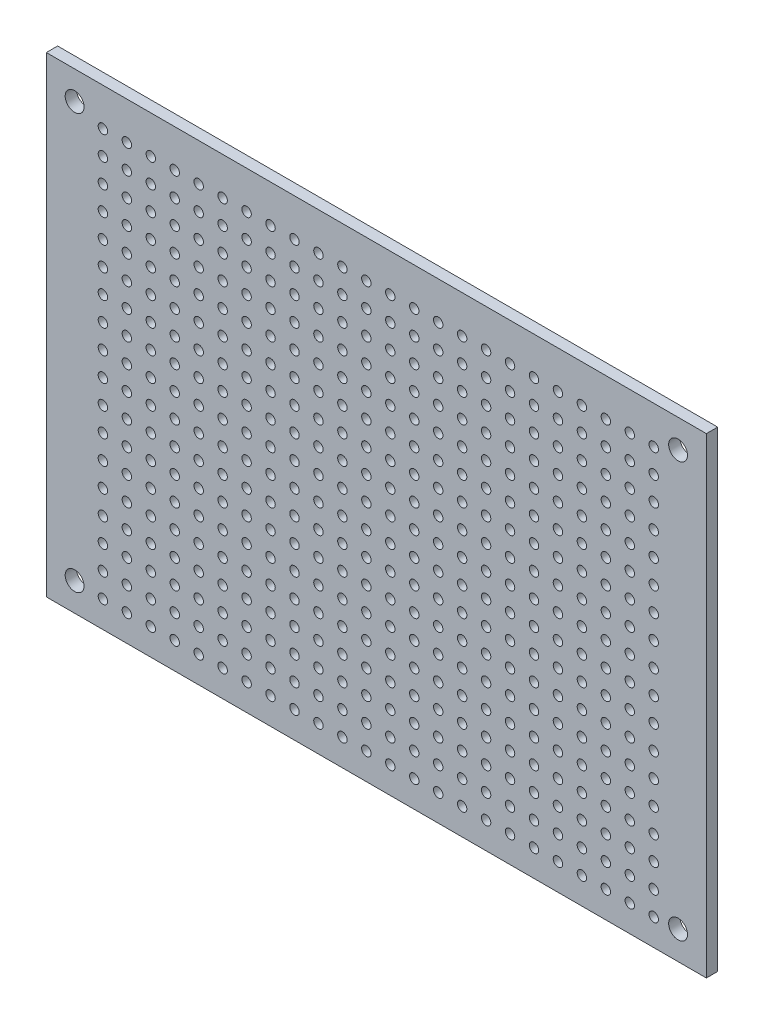
SolidWorks part; units mm, degrees
material "Ст 3 ГОСТ 380-88"
ref_plane "FRONT" through (0, 0, 0) normal (0, 0, 1) x (1, 0, 0)
ref_plane "TOP" through (0, 0, 0) normal (0, 1, 0) x (1, 0, 0)
ref_plane "RIGHT" through (0, 0, 0) normal (1, 0, 0) x (0, 0, -1)
sketch "Эскиз1" plane through (0, 0, 0) normal (0, 0, 1) x (1, 0, 0)
  line L0 (35, 50) -> (35, 0) construction
  line L1 (0, 0) -> (70, 0)
  line L2 (0, 0) -> (0, 50)
  line L3 (0, 50) -> (70, 50)
  line L4 (70, 0) -> (70, 50)
  line L5 (70, 25) -> (0, 25) construction
  line L6 (6, 46) -> (64.42, 46) construction
  line L7 (6, 46) -> (6, 2.82) construction
  circle A0 centre (6, 46) radius 0.5
  circle A1 centre (3, 47) radius 1
  circle A2 centre (67, 47) radius 1
  circle A3 centre (67, 3) radius 1
  circle A4 centre (3, 3) radius 1
  circle A5 centre (8.54, 46) radius 0.5
  circle A6 centre (11.08, 46) radius 0.5
  circle A7 centre (13.62, 46) radius 0.5
  circle A8 centre (16.16, 46) radius 0.5
  circle A9 centre (18.7, 46) radius 0.5
  circle A10 centre (21.24, 46) radius 0.5
  circle A11 centre (23.78, 46) radius 0.5
  circle A12 centre (26.32, 46) radius 0.5
  circle A13 centre (28.86, 46) radius 0.5
  circle A14 centre (31.4, 46) radius 0.5
  circle A15 centre (33.94, 46) radius 0.5
  circle A16 centre (36.48, 46) radius 0.5
  circle A17 centre (39.02, 46) radius 0.5
  circle A18 centre (41.56, 46) radius 0.5
  circle A19 centre (44.1, 46) radius 0.5
  circle A20 centre (46.64, 46) radius 0.5
  circle A21 centre (49.18, 46) radius 0.5
  circle A22 centre (51.72, 46) radius 0.5
  circle A23 centre (54.26, 46) radius 0.5
  circle A24 centre (56.8, 46) radius 0.5
  circle A25 centre (59.34, 46) radius 0.5
  circle A26 centre (61.88, 46) radius 0.5
  circle A27 centre (64.42, 46) radius 0.5
  circle A28 centre (8.54, 43.46) radius 0.5
  circle A29 centre (11.08, 43.46) radius 0.5
  circle A30 centre (13.62, 43.46) radius 0.5
  circle A31 centre (16.16, 43.46) radius 0.5
  circle A32 centre (18.7, 43.46) radius 0.5
  circle A33 centre (21.24, 43.46) radius 0.5
  circle A34 centre (23.78, 43.46) radius 0.5
  circle A35 centre (26.32, 43.46) radius 0.5
  circle A36 centre (28.86, 43.46) radius 0.5
  circle A37 centre (31.4, 43.46) radius 0.5
  circle A38 centre (33.94, 43.46) radius 0.5
  circle A39 centre (36.48, 43.46) radius 0.5
  circle A40 centre (39.02, 43.46) radius 0.5
  circle A41 centre (41.56, 43.46) radius 0.5
  circle A42 centre (44.1, 43.46) radius 0.5
  circle A43 centre (46.64, 43.46) radius 0.5
  circle A44 centre (49.18, 43.46) radius 0.5
  circle A45 centre (51.72, 43.46) radius 0.5
  circle A46 centre (54.26, 43.46) radius 0.5
  circle A47 centre (56.8, 43.46) radius 0.5
  circle A48 centre (59.34, 43.46) radius 0.5
  circle A49 centre (61.88, 43.46) radius 0.5
  circle A50 centre (64.42, 43.46) radius 0.5
  circle A51 centre (8.54, 40.92) radius 0.5
  circle A52 centre (11.08, 40.92) radius 0.5
  circle A53 centre (13.62, 40.92) radius 0.5
  circle A54 centre (16.16, 40.92) radius 0.5
  circle A55 centre (18.7, 40.92) radius 0.5
  circle A56 centre (21.24, 40.92) radius 0.5
  circle A57 centre (23.78, 40.92) radius 0.5
  circle A58 centre (26.32, 40.92) radius 0.5
  circle A59 centre (28.86, 40.92) radius 0.5
  circle A60 centre (31.4, 40.92) radius 0.5
  circle A61 centre (33.94, 40.92) radius 0.5
  circle A62 centre (36.48, 40.92) radius 0.5
  circle A63 centre (39.02, 40.92) radius 0.5
  circle A64 centre (41.56, 40.92) radius 0.5
  circle A65 centre (44.1, 40.92) radius 0.5
  circle A66 centre (46.64, 40.92) radius 0.5
  circle A67 centre (49.18, 40.92) radius 0.5
  circle A68 centre (51.72, 40.92) radius 0.5
  circle A69 centre (54.26, 40.92) radius 0.5
  circle A70 centre (56.8, 40.92) radius 0.5
  circle A71 centre (59.34, 40.92) radius 0.5
  circle A72 centre (61.88, 40.92) radius 0.5
  circle A73 centre (64.42, 40.92) radius 0.5
  circle A74 centre (8.54, 38.38) radius 0.5
  circle A75 centre (11.08, 38.38) radius 0.5
  circle A76 centre (13.62, 38.38) radius 0.5
  circle A77 centre (16.16, 38.38) radius 0.5
  circle A78 centre (18.7, 38.38) radius 0.5
  circle A79 centre (21.24, 38.38) radius 0.5
  circle A80 centre (23.78, 38.38) radius 0.5
  circle A81 centre (26.32, 38.38) radius 0.5
  circle A82 centre (28.86, 38.38) radius 0.5
  circle A83 centre (31.4, 38.38) radius 0.5
  circle A84 centre (33.94, 38.38) radius 0.5
  circle A85 centre (36.48, 38.38) radius 0.5
  circle A86 centre (39.02, 38.38) radius 0.5
  circle A87 centre (41.56, 38.38) radius 0.5
  circle A88 centre (44.1, 38.38) radius 0.5
  circle A89 centre (46.64, 38.38) radius 0.5
  circle A90 centre (49.18, 38.38) radius 0.5
  circle A91 centre (51.72, 38.38) radius 0.5
  circle A92 centre (54.26, 38.38) radius 0.5
  circle A93 centre (56.8, 38.38) radius 0.5
  circle A94 centre (59.34, 38.38) radius 0.5
  circle A95 centre (61.88, 38.38) radius 0.5
  circle A96 centre (64.42, 38.38) radius 0.5
  circle A97 centre (8.54, 35.84) radius 0.5
  circle A98 centre (11.08, 35.84) radius 0.5
  circle A99 centre (13.62, 35.84) radius 0.5
  circle A100 centre (16.16, 35.84) radius 0.5
  circle A101 centre (18.7, 35.84) radius 0.5
  circle A102 centre (21.24, 35.84) radius 0.5
  circle A103 centre (23.78, 35.84) radius 0.5
  circle A104 centre (26.32, 35.84) radius 0.5
  circle A105 centre (28.86, 35.84) radius 0.5
  circle A106 centre (31.4, 35.84) radius 0.5
  circle A107 centre (33.94, 35.84) radius 0.5
  circle A108 centre (36.48, 35.84) radius 0.5
  circle A109 centre (39.02, 35.84) radius 0.5
  circle A110 centre (41.56, 35.84) radius 0.5
  circle A111 centre (44.1, 35.84) radius 0.5
  circle A112 centre (46.64, 35.84) radius 0.5
  circle A113 centre (49.18, 35.84) radius 0.5
  circle A114 centre (51.72, 35.84) radius 0.5
  circle A115 centre (54.26, 35.84) radius 0.5
  circle A116 centre (56.8, 35.84) radius 0.5
  circle A117 centre (59.34, 35.84) radius 0.5
  circle A118 centre (61.88, 35.84) radius 0.5
  circle A119 centre (64.42, 35.84) radius 0.5
  circle A120 centre (8.54, 33.3) radius 0.5
  circle A121 centre (11.08, 33.3) radius 0.5
  circle A122 centre (13.62, 33.3) radius 0.5
  circle A123 centre (16.16, 33.3) radius 0.5
  circle A124 centre (18.7, 33.3) radius 0.5
  circle A125 centre (21.24, 33.3) radius 0.5
  circle A126 centre (23.78, 33.3) radius 0.5
  circle A127 centre (26.32, 33.3) radius 0.5
  circle A128 centre (28.86, 33.3) radius 0.5
  circle A129 centre (31.4, 33.3) radius 0.5
  circle A130 centre (33.94, 33.3) radius 0.5
  circle A131 centre (36.48, 33.3) radius 0.5
  circle A132 centre (39.02, 33.3) radius 0.5
  circle A133 centre (41.56, 33.3) radius 0.5
  circle A134 centre (44.1, 33.3) radius 0.5
  circle A135 centre (46.64, 33.3) radius 0.5
  circle A136 centre (49.18, 33.3) radius 0.5
  circle A137 centre (51.72, 33.3) radius 0.5
  circle A138 centre (54.26, 33.3) radius 0.5
  circle A139 centre (56.8, 33.3) radius 0.5
  circle A140 centre (59.34, 33.3) radius 0.5
  circle A141 centre (61.88, 33.3) radius 0.5
  circle A142 centre (64.42, 33.3) radius 0.5
  circle A143 centre (8.54, 30.76) radius 0.5
  circle A144 centre (11.08, 30.76) radius 0.5
  circle A145 centre (13.62, 30.76) radius 0.5
  circle A146 centre (16.16, 30.76) radius 0.5
  circle A147 centre (18.7, 30.76) radius 0.5
  circle A148 centre (21.24, 30.76) radius 0.5
  circle A149 centre (23.78, 30.76) radius 0.5
  circle A150 centre (26.32, 30.76) radius 0.5
  circle A151 centre (28.86, 30.76) radius 0.5
  circle A152 centre (31.4, 30.76) radius 0.5
  circle A153 centre (33.94, 30.76) radius 0.5
  circle A154 centre (36.48, 30.76) radius 0.5
  circle A155 centre (39.02, 30.76) radius 0.5
  circle A156 centre (41.56, 30.76) radius 0.5
  circle A157 centre (44.1, 30.76) radius 0.5
  circle A158 centre (46.64, 30.76) radius 0.5
  circle A159 centre (49.18, 30.76) radius 0.5
  circle A160 centre (51.72, 30.76) radius 0.5
  circle A161 centre (54.26, 30.76) radius 0.5
  circle A162 centre (56.8, 30.76) radius 0.5
  circle A163 centre (59.34, 30.76) radius 0.5
  circle A164 centre (61.88, 30.76) radius 0.5
  circle A165 centre (64.42, 30.76) radius 0.5
  circle A166 centre (8.54, 28.22) radius 0.5
  circle A167 centre (11.08, 28.22) radius 0.5
  circle A168 centre (13.62, 28.22) radius 0.5
  circle A169 centre (16.16, 28.22) radius 0.5
  circle A170 centre (18.7, 28.22) radius 0.5
  circle A171 centre (21.24, 28.22) radius 0.5
  circle A172 centre (23.78, 28.22) radius 0.5
  circle A173 centre (26.32, 28.22) radius 0.5
  circle A174 centre (28.86, 28.22) radius 0.5
  circle A175 centre (31.4, 28.22) radius 0.5
  circle A176 centre (33.94, 28.22) radius 0.5
  circle A177 centre (36.48, 28.22) radius 0.5
  circle A178 centre (39.02, 28.22) radius 0.5
  circle A179 centre (41.56, 28.22) radius 0.5
  circle A180 centre (44.1, 28.22) radius 0.5
  circle A181 centre (46.64, 28.22) radius 0.5
  circle A182 centre (49.18, 28.22) radius 0.5
  circle A183 centre (51.72, 28.22) radius 0.5
  circle A184 centre (54.26, 28.22) radius 0.5
  circle A185 centre (56.8, 28.22) radius 0.5
  circle A186 centre (59.34, 28.22) radius 0.5
  circle A187 centre (61.88, 28.22) radius 0.5
  circle A188 centre (64.42, 28.22) radius 0.5
  circle A189 centre (8.54, 25.68) radius 0.5
  circle A190 centre (11.08, 25.68) radius 0.5
  circle A191 centre (13.62, 25.68) radius 0.5
  circle A192 centre (16.16, 25.68) radius 0.5
  circle A193 centre (18.7, 25.68) radius 0.5
  circle A194 centre (21.24, 25.68) radius 0.5
  circle A195 centre (23.78, 25.68) radius 0.5
  circle A196 centre (26.32, 25.68) radius 0.5
  circle A197 centre (28.86, 25.68) radius 0.5
  circle A198 centre (31.4, 25.68) radius 0.5
  circle A199 centre (33.94, 25.68) radius 0.5
  circle A200 centre (36.48, 25.68) radius 0.5
  circle A201 centre (39.02, 25.68) radius 0.5
  circle A202 centre (41.56, 25.68) radius 0.5
  circle A203 centre (44.1, 25.68) radius 0.5
  circle A204 centre (46.64, 25.68) radius 0.5
  circle A205 centre (49.18, 25.68) radius 0.5
  circle A206 centre (51.72, 25.68) radius 0.5
  circle A207 centre (54.26, 25.68) radius 0.5
  circle A208 centre (56.8, 25.68) radius 0.5
  circle A209 centre (59.34, 25.68) radius 0.5
  circle A210 centre (61.88, 25.68) radius 0.5
  circle A211 centre (64.42, 25.68) radius 0.5
  circle A212 centre (8.54, 23.14) radius 0.5
  circle A213 centre (11.08, 23.14) radius 0.5
  circle A214 centre (13.62, 23.14) radius 0.5
  circle A215 centre (16.16, 23.14) radius 0.5
  circle A216 centre (18.7, 23.14) radius 0.5
  circle A217 centre (21.24, 23.14) radius 0.5
  circle A218 centre (23.78, 23.14) radius 0.5
  circle A219 centre (26.32, 23.14) radius 0.5
  circle A220 centre (28.86, 23.14) radius 0.5
  circle A221 centre (31.4, 23.14) radius 0.5
  circle A222 centre (33.94, 23.14) radius 0.5
  circle A223 centre (36.48, 23.14) radius 0.5
  circle A224 centre (39.02, 23.14) radius 0.5
  circle A225 centre (41.56, 23.14) radius 0.5
  circle A226 centre (44.1, 23.14) radius 0.5
  circle A227 centre (46.64, 23.14) radius 0.5
  circle A228 centre (49.18, 23.14) radius 0.5
  circle A229 centre (51.72, 23.14) radius 0.5
  circle A230 centre (54.26, 23.14) radius 0.5
  circle A231 centre (56.8, 23.14) radius 0.5
  circle A232 centre (59.34, 23.14) radius 0.5
  circle A233 centre (61.88, 23.14) radius 0.5
  circle A234 centre (64.42, 23.14) radius 0.5
  circle A235 centre (8.54, 20.6) radius 0.5
  circle A236 centre (11.08, 20.6) radius 0.5
  circle A237 centre (13.62, 20.6) radius 0.5
  circle A238 centre (16.16, 20.6) radius 0.5
  circle A239 centre (18.7, 20.6) radius 0.5
  circle A240 centre (21.24, 20.6) radius 0.5
  circle A241 centre (23.78, 20.6) radius 0.5
  circle A242 centre (26.32, 20.6) radius 0.5
  circle A243 centre (28.86, 20.6) radius 0.5
  circle A244 centre (31.4, 20.6) radius 0.5
  circle A245 centre (33.94, 20.6) radius 0.5
  circle A246 centre (36.48, 20.6) radius 0.5
  circle A247 centre (39.02, 20.6) radius 0.5
  circle A248 centre (41.56, 20.6) radius 0.5
  circle A249 centre (44.1, 20.6) radius 0.5
  circle A250 centre (46.64, 20.6) radius 0.5
  circle A251 centre (49.18, 20.6) radius 0.5
  circle A252 centre (51.72, 20.6) radius 0.5
  circle A253 centre (54.26, 20.6) radius 0.5
  circle A254 centre (56.8, 20.6) radius 0.5
  circle A255 centre (59.34, 20.6) radius 0.5
  circle A256 centre (61.88, 20.6) radius 0.5
  circle A257 centre (64.42, 20.6) radius 0.5
  circle A258 centre (8.54, 18.06) radius 0.5
  circle A259 centre (11.08, 18.06) radius 0.5
  circle A260 centre (13.62, 18.06) radius 0.5
  circle A261 centre (16.16, 18.06) radius 0.5
  circle A262 centre (18.7, 18.06) radius 0.5
  circle A263 centre (21.24, 18.06) radius 0.5
  circle A264 centre (23.78, 18.06) radius 0.5
  circle A265 centre (26.32, 18.06) radius 0.5
  circle A266 centre (28.86, 18.06) radius 0.5
  circle A267 centre (31.4, 18.06) radius 0.5
  circle A268 centre (33.94, 18.06) radius 0.5
  circle A269 centre (36.48, 18.06) radius 0.5
  circle A270 centre (39.02, 18.06) radius 0.5
  circle A271 centre (41.56, 18.06) radius 0.5
  circle A272 centre (44.1, 18.06) radius 0.5
  circle A273 centre (46.64, 18.06) radius 0.5
  circle A274 centre (49.18, 18.06) radius 0.5
  circle A275 centre (51.72, 18.06) radius 0.5
  circle A276 centre (54.26, 18.06) radius 0.5
  circle A277 centre (56.8, 18.06) radius 0.5
  circle A278 centre (59.34, 18.06) radius 0.5
  circle A279 centre (61.88, 18.06) radius 0.5
  circle A280 centre (64.42, 18.06) radius 0.5
  circle A281 centre (8.54, 15.52) radius 0.5
  circle A282 centre (11.08, 15.52) radius 0.5
  circle A283 centre (13.62, 15.52) radius 0.5
  circle A284 centre (16.16, 15.52) radius 0.5
  circle A285 centre (18.7, 15.52) radius 0.5
  circle A286 centre (21.24, 15.52) radius 0.5
  circle A287 centre (23.78, 15.52) radius 0.5
  circle A288 centre (26.32, 15.52) radius 0.5
  circle A289 centre (28.86, 15.52) radius 0.5
  circle A290 centre (31.4, 15.52) radius 0.5
  circle A291 centre (33.94, 15.52) radius 0.5
  circle A292 centre (36.48, 15.52) radius 0.5
  circle A293 centre (39.02, 15.52) radius 0.5
  circle A294 centre (41.56, 15.52) radius 0.5
  circle A295 centre (44.1, 15.52) radius 0.5
  circle A296 centre (46.64, 15.52) radius 0.5
  circle A297 centre (49.18, 15.52) radius 0.5
  circle A298 centre (51.72, 15.52) radius 0.5
  circle A299 centre (54.26, 15.52) radius 0.5
  circle A300 centre (56.8, 15.52) radius 0.5
  circle A301 centre (59.34, 15.52) radius 0.5
  circle A302 centre (61.88, 15.52) radius 0.5
  circle A303 centre (64.42, 15.52) radius 0.5
  circle A304 centre (8.54, 12.98) radius 0.5
  circle A305 centre (11.08, 12.98) radius 0.5
  circle A306 centre (13.62, 12.98) radius 0.5
  circle A307 centre (16.16, 12.98) radius 0.5
  circle A308 centre (18.7, 12.98) radius 0.5
  circle A309 centre (21.24, 12.98) radius 0.5
  circle A310 centre (23.78, 12.98) radius 0.5
  circle A311 centre (26.32, 12.98) radius 0.5
  circle A312 centre (28.86, 12.98) radius 0.5
  circle A313 centre (31.4, 12.98) radius 0.5
  circle A314 centre (33.94, 12.98) radius 0.5
  circle A315 centre (36.48, 12.98) radius 0.5
  circle A316 centre (39.02, 12.98) radius 0.5
  circle A317 centre (41.56, 12.98) radius 0.5
  circle A318 centre (44.1, 12.98) radius 0.5
  circle A319 centre (46.64, 12.98) radius 0.5
  circle A320 centre (49.18, 12.98) radius 0.5
  circle A321 centre (51.72, 12.98) radius 0.5
  circle A322 centre (54.26, 12.98) radius 0.5
  circle A323 centre (56.8, 12.98) radius 0.5
  circle A324 centre (59.34, 12.98) radius 0.5
  circle A325 centre (61.88, 12.98) radius 0.5
  circle A326 centre (64.42, 12.98) radius 0.5
  circle A327 centre (8.54, 10.44) radius 0.5
  circle A328 centre (11.08, 10.44) radius 0.5
  circle A329 centre (13.62, 10.44) radius 0.5
  circle A330 centre (16.16, 10.44) radius 0.5
  circle A331 centre (18.7, 10.44) radius 0.5
  circle A332 centre (21.24, 10.44) radius 0.5
  circle A333 centre (23.78, 10.44) radius 0.5
  circle A334 centre (26.32, 10.44) radius 0.5
  circle A335 centre (28.86, 10.44) radius 0.5
  circle A336 centre (31.4, 10.44) radius 0.5
  circle A337 centre (33.94, 10.44) radius 0.5
  circle A338 centre (36.48, 10.44) radius 0.5
  circle A339 centre (39.02, 10.44) radius 0.5
  circle A340 centre (41.56, 10.44) radius 0.5
  circle A341 centre (44.1, 10.44) radius 0.5
  circle A342 centre (46.64, 10.44) radius 0.5
  circle A343 centre (49.18, 10.44) radius 0.5
  circle A344 centre (51.72, 10.44) radius 0.5
  circle A345 centre (54.26, 10.44) radius 0.5
  circle A346 centre (56.8, 10.44) radius 0.5
  circle A347 centre (59.34, 10.44) radius 0.5
  circle A348 centre (61.88, 10.44) radius 0.5
  circle A349 centre (64.42, 10.44) radius 0.5
  circle A350 centre (8.54, 7.9) radius 0.5
  circle A351 centre (11.08, 7.9) radius 0.5
  circle A352 centre (13.62, 7.9) radius 0.5
  circle A353 centre (16.16, 7.9) radius 0.5
  circle A354 centre (18.7, 7.9) radius 0.5
  circle A355 centre (21.24, 7.9) radius 0.5
  circle A356 centre (23.78, 7.9) radius 0.5
  circle A357 centre (26.32, 7.9) radius 0.5
  circle A358 centre (28.86, 7.9) radius 0.5
  circle A359 centre (31.4, 7.9) radius 0.5
  circle A360 centre (33.94, 7.9) radius 0.5
  circle A361 centre (36.48, 7.9) radius 0.5
  circle A362 centre (39.02, 7.9) radius 0.5
  circle A363 centre (41.56, 7.9) radius 0.5
  circle A364 centre (44.1, 7.9) radius 0.5
  circle A365 centre (46.64, 7.9) radius 0.5
  circle A366 centre (49.18, 7.9) radius 0.5
  circle A367 centre (51.72, 7.9) radius 0.5
  circle A368 centre (54.26, 7.9) radius 0.5
  circle A369 centre (56.8, 7.9) radius 0.5
  circle A370 centre (59.34, 7.9) radius 0.5
  circle A371 centre (61.88, 7.9) radius 0.5
  circle A372 centre (64.42, 7.9) radius 0.5
  circle A373 centre (8.54, 5.36) radius 0.5
  circle A374 centre (11.08, 5.36) radius 0.5
  circle A375 centre (13.62, 5.36) radius 0.5
  circle A376 centre (16.16, 5.36) radius 0.5
  circle A377 centre (18.7, 5.36) radius 0.5
  circle A378 centre (21.24, 5.36) radius 0.5
  circle A379 centre (23.78, 5.36) radius 0.5
  circle A380 centre (26.32, 5.36) radius 0.5
  circle A381 centre (28.86, 5.36) radius 0.5
  circle A382 centre (31.4, 5.36) radius 0.5
  circle A383 centre (33.94, 5.36) radius 0.5
  circle A384 centre (36.48, 5.36) radius 0.5
  circle A385 centre (39.02, 5.36) radius 0.5
  circle A386 centre (41.56, 5.36) radius 0.5
  circle A387 centre (44.1, 5.36) radius 0.5
  circle A388 centre (46.64, 5.36) radius 0.5
  circle A389 centre (49.18, 5.36) radius 0.5
  circle A390 centre (51.72, 5.36) radius 0.5
  circle A391 centre (54.26, 5.36) radius 0.5
  circle A392 centre (56.8, 5.36) radius 0.5
  circle A393 centre (59.34, 5.36) radius 0.5
  circle A394 centre (61.88, 5.36) radius 0.5
  circle A395 centre (64.42, 5.36) radius 0.5
  circle A396 centre (8.54, 2.82) radius 0.5
  circle A397 centre (11.08, 2.82) radius 0.5
  circle A398 centre (13.62, 2.82) radius 0.5
  circle A399 centre (16.16, 2.82) radius 0.5
  circle A400 centre (18.7, 2.82) radius 0.5
  circle A401 centre (21.24, 2.82) radius 0.5
  circle A402 centre (23.78, 2.82) radius 0.5
  circle A403 centre (26.32, 2.82) radius 0.5
  circle A404 centre (28.86, 2.82) radius 0.5
  circle A405 centre (31.4, 2.82) radius 0.5
  circle A406 centre (33.94, 2.82) radius 0.5
  circle A407 centre (36.48, 2.82) radius 0.5
  circle A408 centre (39.02, 2.82) radius 0.5
  circle A409 centre (41.56, 2.82) radius 0.5
  circle A410 centre (44.1, 2.82) radius 0.5
  circle A411 centre (46.64, 2.82) radius 0.5
  circle A412 centre (49.18, 2.82) radius 0.5
  circle A413 centre (51.72, 2.82) radius 0.5
  circle A414 centre (54.26, 2.82) radius 0.5
  circle A415 centre (56.8, 2.82) radius 0.5
  circle A416 centre (59.34, 2.82) radius 0.5
  circle A417 centre (61.88, 2.82) radius 0.5
  circle A418 centre (64.42, 2.82) radius 0.5
  circle A419 centre (6, 43.46) radius 0.5
  circle A420 centre (6, 40.92) radius 0.5
  circle A421 centre (6, 38.38) radius 0.5
  circle A422 centre (6, 35.84) radius 0.5
  circle A423 centre (6, 33.3) radius 0.5
  circle A424 centre (6, 30.76) radius 0.5
  circle A425 centre (6, 28.22) radius 0.5
  circle A426 centre (6, 25.68) radius 0.5
  circle A427 centre (6, 23.14) radius 0.5
  circle A428 centre (6, 20.6) radius 0.5
  circle A429 centre (6, 18.06) radius 0.5
  circle A430 centre (6, 15.52) radius 0.5
  circle A431 centre (6, 12.98) radius 0.5
  circle A432 centre (6, 10.44) radius 0.5
  circle A433 centre (6, 7.9) radius 0.5
  circle A434 centre (6, 5.36) radius 0.5
  circle A435 centre (6, 2.82) radius 0.5
  dimension "D3" = 1
  dimension "D4" = 4
  dimension "D5" = 6
  dimension "D6" = 3
  dimension "D7" = 3
  dimension "D8" = 2
  dimension "D9" = 64
  dimension "D10" = 44
  dimension "D13" = 2.54
  dimension "D14" = 2.54
  dimension "D1" = 70
  dimension "D2" = 50
  dimension "D11" = 24
  dimension "D12" = 18
extrude "Бобышка-Вытянуть1" add sketch "Эскиз1" along normal blind 1.2
sketch "Эскиз2" plane through (0, 0, 1.2) normal (0, 0, 1) x (1, 0, 0)
  line L1 (6, 46) -> (64.42, 46)
  line L2 (6, 46) -> (6, 2.82)
  line L3 (6, 2.82) -> (64.42, 2.82)
  line L4 (64.42, 46) -> (64.42, 2.82)
extrude "Вырез-Вытянуть-Тонкостенный1" [suppressed] cut sketch "Эскиз2" against normal blind 0.1 thin thin type mid plane wall 0.1
sketch "Эскиз3" plane through (0, 0, 1.2) normal (0, 0, 1) x (1, 0, 0)
  line L0 (13.62, 46) -> (13.62, 2.82)
  line L1 (23.78, 2.82) -> (23.78, 46)
  line L2 (33.94, 46) -> (33.94, 2.82)
  line L3 (44.1, 2.82) -> (44.1, 46)
  line L4 (54.26, 46) -> (54.26, 2.82)
  line L5 (6, 33.3) -> (64.42, 33.3)
  line L6 (6, 23.14) -> (64.42, 23.14)
  line L7 (6, 12.98) -> (64.42, 12.98)
extrude "Вырез-Вытянуть-Тонкостенный2" [suppressed] cut sketch "Эскиз3" against normal blind 0.1 thin thin type one direction wall 0.1
sketch "Эскиз4" plane through (0, 0, 1.2) normal (0, 0, 1) x (1, 0, 0)
  line L0 (4.9874, 47.6456) -> (65.2677, 47.6456) construction
  line L1 (4.9874, 0.2403) -> (65.2677, 0.2403) construction
  line L3 (67.2067, 45.3105) -> (67.2067, 2.8617) construction
  line L4 (1.5401, 45.3105) -> (1.5401, 2.8617) construction
  text T0 "01 02 03 04 05 06 07 08 09 10 11 12 13 14 15 16 17 18 19 20 21 22 23 24" font "@Arial Unicode MS" height 1.5
  text T1 "01 02 03 04 05 06 07 08 09 10 11 12 13 14 15 16 17 18 19 20 21 22 23 24" font "@Arial Unicode MS" height 1.5
  text T2 "<r90>A B C D E F G H I J K L M N O P Q</r>" font "@Arial Unicode MS" height 1.5
  text T3 "<r90>A B C D E F G H I J K L M N O P Q</r>" font "@Arial Unicode MS" height 1.5
extrude "Вырез-Вытянуть1" [suppressed] cut sketch "Эскиз4" against normal blind 0.1
